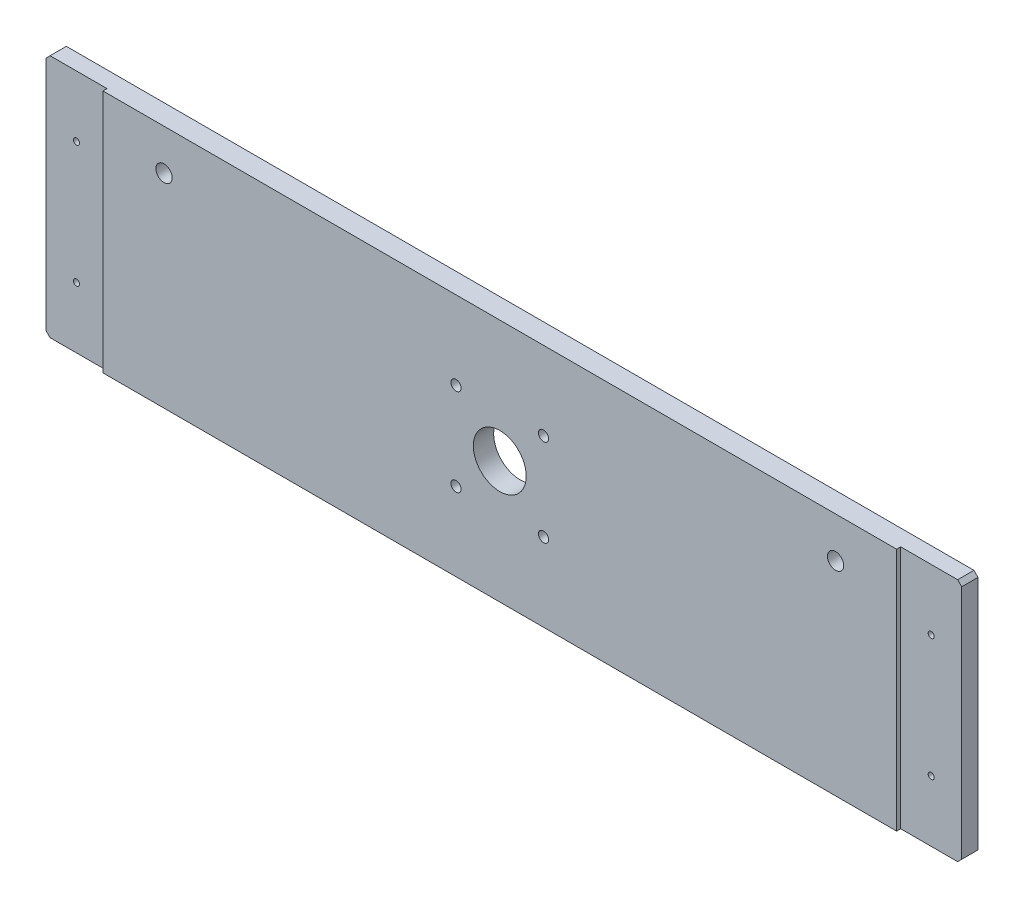
SolidWorks part; units mm, degrees
ref_plane "Piano frontale" through (0, 0, 0) normal (0, 0, 1) x (1, 0, 0)
ref_plane "Piano superiore" through (0, 0, 0) normal (0, 1, 0) x (1, 0, 0)
ref_plane "Piano destro" through (0, 0, 0) normal (1, 0, 0) x (0, 0, -1)
sketch "Schizzo1" plane through (0, 0, 0) normal (0, 0, 1) x (1, 0, 0)
  line L0 (225, 120) -> (225, 0) construction
  line L1 (2, 0) -> (448, 0)
  line L2 (0, 2) -> (0, 118)
  line L3 (2, 120) -> (448, 120)
  line L4 (450, 2) -> (450, 118)
  line L5 (203.5, 62.7163) -> (203.5, 15.9855) construction
  line L6 (250.0723, 81.5) -> (199.9971, 81.5) construction
  line L7 (225, 60) -> (243.5099, 60) construction
  line L8 (459.2931, 100) -> (370.8276, 100) construction
  line L21 (0, 118) -> (2, 120)
  line L22 (2, 0) -> (0, 2)
  line L23 (448, 0) -> (450, 2)
  line L24 (448, 120) -> (450, 118)
  line L25 (225, 60) -> (450, 60) construction
  circle A0 centre (225, 60) radius 13
  circle A3 centre (390, 100) radius 4
  circle A10 centre (60, 100) radius 4
  circle A11 centre (15, 30) radius 1.5
  circle A12 centre (435, 30) radius 1.5
  circle A13 centre (203.5, 81.5) radius 2.5
  circle A14 centre (246.5, 81.5) radius 2.5
  circle A15 centre (246.5, 38.5) radius 2.5
  circle A16 centre (203.5, 38.5) radius 2.5
  circle A17 centre (435, 90) radius 1.5
  circle A18 centre (15, 90) radius 1.5
  point P0 (0, 0)
  point P1 (450, 120)
  point P2 (0, 120)
  point P3 (450, 0)
  point P13 (203.5, 81.5)
  point P14 (246.5, 81.5)
  point P15 (203.5, 38.5)
  point P17 (246.5, 38.5)
  dimension "D4" = 26
  dimension "D10" = 8
  dimension "D15" = 3
  dimension "D17" = 5
  dimension "D1" = 120
  dimension "D2" = 450
  dimension "D3" = 60
  dimension "D5" = 21.5
  dimension "D6" = 21.5
  dimension "D7" = 20
  dimension "D12" = 60
  dimension "D14" = 30
  dimension "D16" = 15
extrude "Estrusione-Estrusione1" add sketch "Schizzo1" against normal blind 10
sketch "Schizzo2" plane through (0, 0, 0) normal (0, 0, 1) x (1, 0, 0)
  line L0 (448, 120) -> (2, 120) construction
  line L1 (30, 120) -> (0, 120)
  line L2 (30, 120) -> (30, 0)
  line L3 (30, 0) -> (0, 0)
  line L4 (0, 120) -> (0, 0)
  line L5 (225, 120) -> (225, -23.5993) construction
  line L6 (450, 120) -> (450, 0)
  line L7 (420, 0) -> (450, 0)
  line L8 (420, 120) -> (420, 0)
  line L9 (420, 120) -> (450, 120)
  dimension "D1" = 30
extrude "Taglio-Estrusione1" cut sketch "Schizzo2" against normal blind 2
